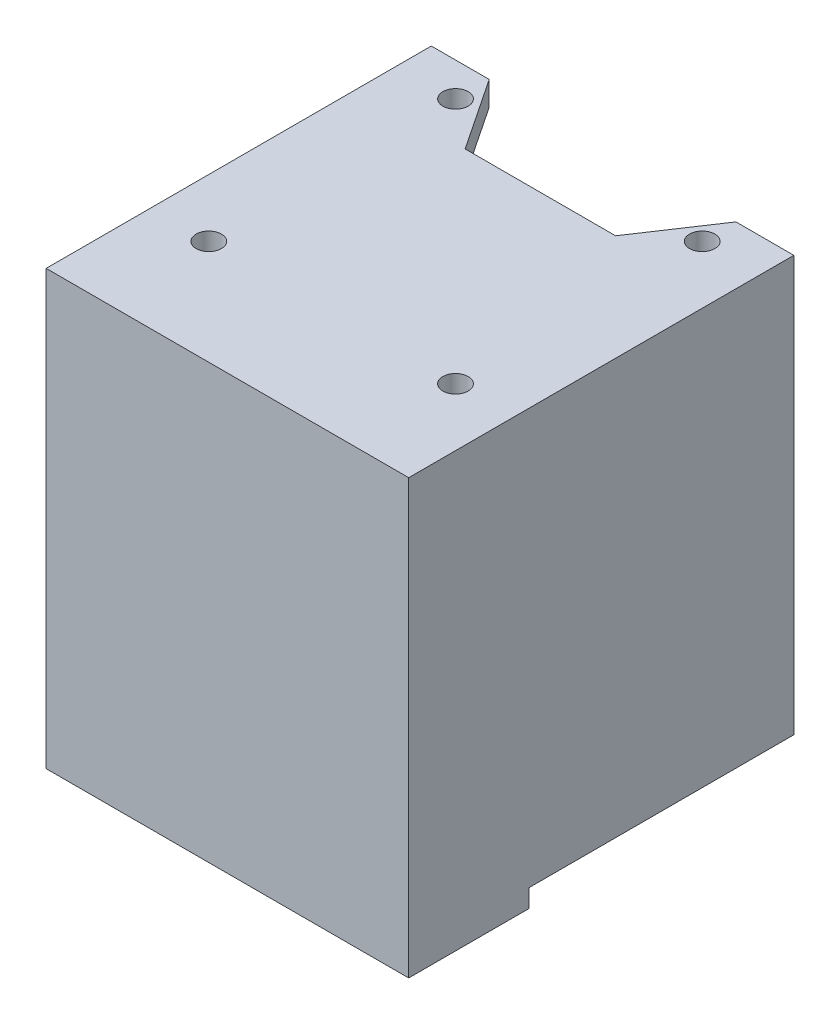
SolidWorks part; units mm, degrees
ref_plane "Front Plane" through (0, 0, 0) normal (0, 0, 1) x (1, 0, 0)
ref_plane "Top Plane" through (0, 0, 0) normal (0, 1, 0) x (1, 0, 0)
ref_plane "Right Plane" through (0, 0, 0) normal (1, 0, 0) x (0, 0, -1)
sketch "Sketch2" plane through (0, 0, 0) normal (0, 1, 0) x (1, 0, 0)
  line L0 (15.061, 0) -> (15.061, 32)
  line L1 (-12.561, 2.5) -> (12.561, 2.5)
  line L2 (-12.561, 2.5) -> (-12.561, 32)
  line L4 (12.561, 2.5) -> (12.561, 32)
  line L5 (15.061, 32) -> (12.561, 32)
  line L7 (-15.061, 32) -> (-15.061, 0)
  line L8 (-15.061, 0) -> (15.061, 0)
  line L10 (-15.061, 32) -> (-12.561, 32)
  point P4 (0, 2.5)
  point P12 (0, 0)
  dimension "D1" = 2.5
  dimension "D2" = 2.5
  dimension "D3" = 29.5
  dimension "D4" = 25.122
extrude "Boss-Extrude1" add sketch "Sketch2" along normal blind 32.5
sketch "Sketch4" plane through (0, 0, 0) normal (0, -1, 0) x (1, 0, 0)
  line L4 (-7.5, -6) -> (7.5, -6)
  line L9 (15.061, 0) -> (-15.061, 0)
  line L13 (-12.561, -2.5) -> (-12.561, -32) construction
  line L18 (-12.561, -10) -> (-7.5, -6)
  line L23 (12.561, -32) -> (12.561, -2.5) construction
  line L26 (12.561, -10) -> (7.5, -6)
  line L32 (-12.561, -10) -> (-15.061, -10)
  line L33 (-15.061, -32) -> (-15.061, 0) construction
  line L34 (-15.061, -10) -> (-15.061, 0)
  line L35 (12.561, -10) -> (15.061, -10)
  line L36 (15.061, 0) -> (15.061, -32) construction
  line L37 (15.061, -10) -> (15.061, 0)
  circle A2 centre (-10.2499, -4.95) radius 1.05
  circle A5 centre (10.2499, -4.95) radius 1.05
  point P31 (0, -6)
  dimension "D5" = 2.1
  dimension "D10" = 15
  dimension "D11" = 10
  dimension "D2" = 6
  dimension "D7" = 4.95
extrude "Boss-Extrude2" add sketch "Sketch4" along normal blind 1.5
sketch "Sketch5" plane through (0, 32.5, 0) normal (0, 1, 0) x (1, 0, 0)
  line L0 (-15.061, 32) -> (-10.2499, 32)
  line L9 (-10.2499, 32) -> (-6.25, 26)
  line L13 (-15.061, 0) -> (15.061, 0) construction
  line L14 (15.061, 0) -> (-15.061, 0)
  line L15 (-15.061, 0) -> (-15.061, 32)
  line L20 (15.061, 0) -> (15.061, 32)
  line L21 (-6.25, 26) -> (6.25, 26)
  line L22 (6.25, 26) -> (10.2499, 32)
  line L23 (10.2499, 32) -> (15.061, 32)
  circle A0 centre (-10.2499, 4.95) radius 1.05 construction
  circle A1 centre (-10.2499, 8.7) radius 1.05
  circle A2 centre (10.2499, 8.7) radius 1.05
  circle A3 centre (-10.2499, 29.2) radius 1.05
  circle A4 centre (10.2499, 29.2) radius 1.05
  point P0 (-10.2499, 32)
  point P6 (0, 26)
  dimension "D4" = 0
  dimension "D1" = 8.7
  dimension "D2" = 12.5
  dimension "D3" = 20.4998
  dimension "D5" = 6
  dimension "D7" = 20.5
extrude "Boss-Extrude3" add sketch "Sketch5" along normal blind 2
